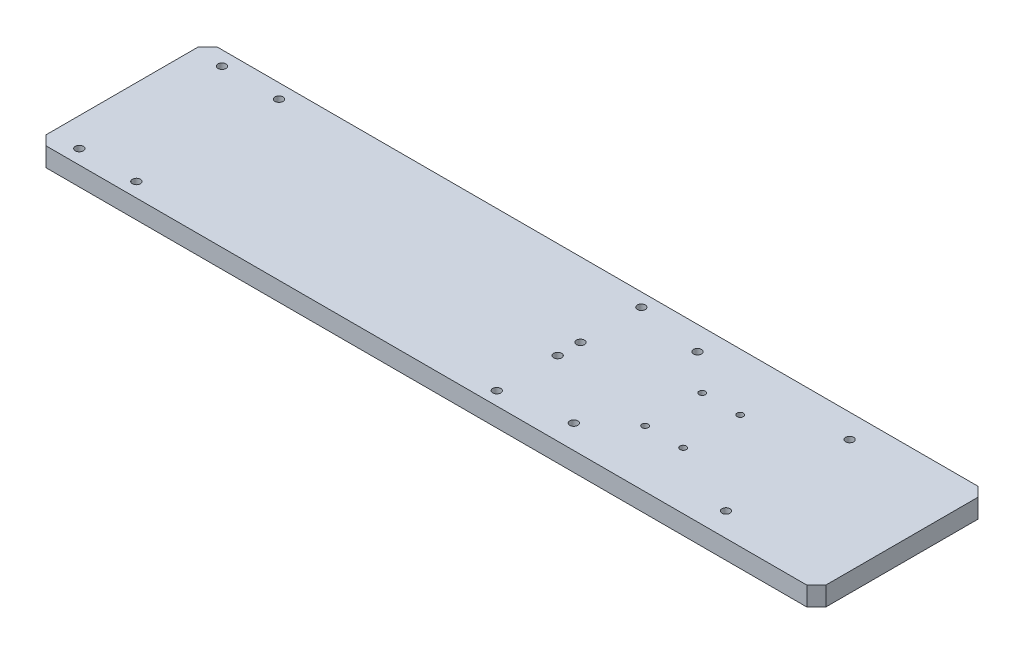
SolidWorks part; units mm, degrees
material "Acrílico (Impacto medio-alto)"
ref_plane "Front Plane" through (0, 0, 0) normal (0, 0, 1) x (1, 0, 0)
ref_plane "Top Plane" through (0, 0, 0) normal (0, 1, 0) x (1, 0, 0)
ref_plane "Right Plane" through (0, 0, 0) normal (1, 0, 0) x (0, 0, -1)
sketch "Croquis1" plane through (0, 0, 0) normal (0, 1, 0) x (1, 0, 0)
  line L1 (0, -45) -> (410, -45)
  line L2 (0, -45) -> (0, 45)
  line L3 (0, 45) -> (410, 45)
  line L4 (410, -45) -> (410, 45)
  line L5 (0, -45) -> (410, 45) construction
  line L6 (0, 45) -> (410, -45) construction
  dimension "D1" = 410
  dimension "D2" = 90
extrude "Saliente-Extruir1" add sketch "Croquis1" along normal blind 10
chamfer "Chaflán1" distance 5 angle 45 4 edges at (0, 5, -45) (0, 5, 45) (410, 5, 45) (410, 5, -45)
hole_wizard "Taladro roscado M53" positions "Croquis2" profile "Croquis3" tap size "M5" standard "DIN" end condition through all
sketch "Croquis2" plane through (0, 0, 0) normal (0, -1, 0) x (-1, 0, 0)
  line L1 (-45, 37.5) -> (-15, 37.5) construction
  line L2 (-45, 37.5) -> (-45, -37.5) construction
  line L3 (-45, -37.5) -> (-15, -37.5) construction
  line L4 (-15, 37.5) -> (-15, -37.5) construction
  line L5 (-45, 37.5) -> (-15, -37.5) construction
  line L6 (-45, -37.5) -> (-15, 37.5) construction
  line L9 (-55, 43) -> (-5, 43) construction
  line L10 (-55, 43) -> (-55, -43) construction
  line L11 (-55, -43) -> (-5, -43) construction
  line L12 (-5, 43) -> (-5, -43) construction
  line L13 (-55, 43) -> (-5, -43) construction
  line L14 (-55, -43) -> (-5, 43) construction
  point P2 (-15, -37.5)
  point P5 (-45, 37.5)
  point P6 (-45, -37.5)
  point P7 (-15, 37.5)
  point P121 (-30, 0)
  point P203 (-30, 0)
  dimension "D1" = 30
  dimension "D2" = 75
  dimension "D3" = 50
  dimension "D4" = 86
  dimension "D5" = 5
sketch "Croquis3" plane through (15, 0, 37.5) normal (1, 0, 0) x (0, 0, -1)
  line L0 (0, 0) -> (0, 10)
  line L1 (0, 10) -> (2.1, 10)
  line L2 (2.1, 10) -> (2.1, 0)
  line L5 (2.1, 0) -> (0, 0)
  line L11 (0, -6.35) -> (0, 107.95) construction
  dimension "Diámetro de perforador para roscar hasta el siguiente" = 4.2
  dimension "Profundidad de perforador para roscar hasta el siguiente" = 10
cosmetic thread "Rosca de taladro13" parameters "D2"=5
cosmetic thread "Rosca de taladro14" parameters "D2"=5
cosmetic thread "Rosca de taladro15" parameters "D2"=5
cosmetic thread "Rosca de taladro16" parameters "D2"=5
hole_wizard "Taladro roscado M51" positions "Croquis4" profile "Croquis5" tap size "M5" standard "DIN" end condition through all
sketch "Croquis4" plane through (0, 0, 0) normal (0, -1, 0) x (-1, 0, 0)
  line L0 (-235, 38) -> (-235, 6) construction
  line L2 (-235, -6) -> (-235, -38) construction
  line L4 (-235, 6) -> (-235, -6) construction
  line L5 (-55, 43) -> (-55, -43) construction
  point P1 (-235, 38)
  point P2 (-235, 6)
  point P5 (-235, -6)
  point P6 (-235, -38)
  point P16 (-235, 0)
  dimension "D1" = 32
  dimension "D2" = 12
  dimension "D3" = 180
sketch "Croquis5" plane through (235, 0, -38) normal (1, 0, 0) x (0, 0, -1)
  line L0 (0, 0) -> (0, 10)
  line L1 (0, 10) -> (2.1, 10)
  line L2 (2.1, 10) -> (2.1, 0)
  line L5 (2.1, 0) -> (0, 0)
  line L11 (0, -6.35) -> (0, 107.95) construction
  dimension "Diámetro de perforador para roscar hasta el siguiente" = 4.2
  dimension "Profundidad de perforador para roscar hasta el siguiente" = 10
cosmetic thread "Rosca de taladro5" parameters "D2"=5
cosmetic thread "Rosca de taladro6" parameters "D2"=5
cosmetic thread "Rosca de taladro7" parameters "D2"=5
cosmetic thread "Rosca de taladro8" parameters "D2"=5
hole_wizard "Taladro roscado M41" positions "Croquis6" profile "Croquis7" tap size "M4" standard "DIN" end condition through all
sketch "Croquis6" plane through (0, 0, 0) normal (0, -1, 0) x (-1, 0, 0)
  line L1 (-310, -15) -> (-290, -15) construction
  line L2 (-310, -15) -> (-310, 15) construction
  line L3 (-310, 15) -> (-290, 15) construction
  line L4 (-290, -15) -> (-290, 15) construction
  line L5 (-310, -15) -> (-290, 15) construction
  line L6 (-310, 15) -> (-290, -15) construction
  line L7 (-55, 43) -> (-55, -43) construction
  point P2 (-290, 15)
  point P5 (-310, -15)
  point P6 (-310, 15)
  point P7 (-290, -15)
  point P41 (-300, 0)
  dimension "D1" = 235
  dimension "D2" = 20
  dimension "D3" = 30
sketch "Croquis7" plane through (290, 0, -15) normal (1, 0, 0) x (0, 0, -1)
  line L0 (0, 0) -> (0, 10)
  line L1 (0, 10) -> (1.65, 10)
  line L2 (1.65, 10) -> (1.65, 0)
  line L5 (1.65, 0) -> (0, 0)
  line L11 (0, -6.35) -> (0, 107.95) construction
  dimension "Diámetro de perforador para roscar hasta el siguiente" = 3.3
  dimension "Profundidad de perforador para roscar hasta el siguiente" = 10
cosmetic thread "Rosca de taladro9" parameters "D2"=4
cosmetic thread "Rosca de taladro10" parameters "D2"=4
cosmetic thread "Rosca de taladro11" parameters "D2"=4
cosmetic thread "Rosca de taladro12" parameters "D2"=4
hole_wizard "Taladro roscado M52" positions "Croquis8" profile "Croquis9" tap size "M5" standard "DIN" end condition through all
sketch "Croquis8" plane through (0, 0, 0) normal (0, -1, 0) x (-1, 0, 0)
  line L1 (-350, -32.5) -> (-270, -32.5)
  line L2 (-350, -32.5) -> (-350, 32.5)
  line L3 (-350, 32.5) -> (-270, 32.5)
  line L4 (-270, -32.5) -> (-270, 32.5)
  line L5 (-350, -32.5) -> (-270, 32.5) construction
  line L6 (-350, 32.5) -> (-270, -32.5) construction
  point P2 (-270, 32.5)
  point P5 (-350, -32.5)
  point P6 (-350, 32.5)
  point P7 (-270, -32.5)
  point P23 (-310, 0)
  dimension "D1" = 80
  dimension "D2" = 65
  dimension "D3" = 270
sketch "Croquis9" plane through (270, 0, -32.5) normal (1, 0, 0) x (0, 0, -1)
  line L0 (0, 0) -> (0, 10)
  line L1 (0, 10) -> (2.1, 10)
  line L2 (2.1, 10) -> (2.1, 0)
  line L5 (2.1, 0) -> (0, 0)
  line L11 (0, -6.35) -> (0, 107.95) construction
  dimension "Diámetro de perforador para roscar hasta el siguiente" = 4.2
  dimension "Profundidad de perforador para roscar hasta el siguiente" = 10
cosmetic thread "Rosca de taladro1" parameters "D2"=5
cosmetic thread "Rosca de taladro2" parameters "D2"=5
cosmetic thread "Rosca de taladro3" parameters "D2"=5
cosmetic thread "Rosca de taladro4" parameters "D2"=5
